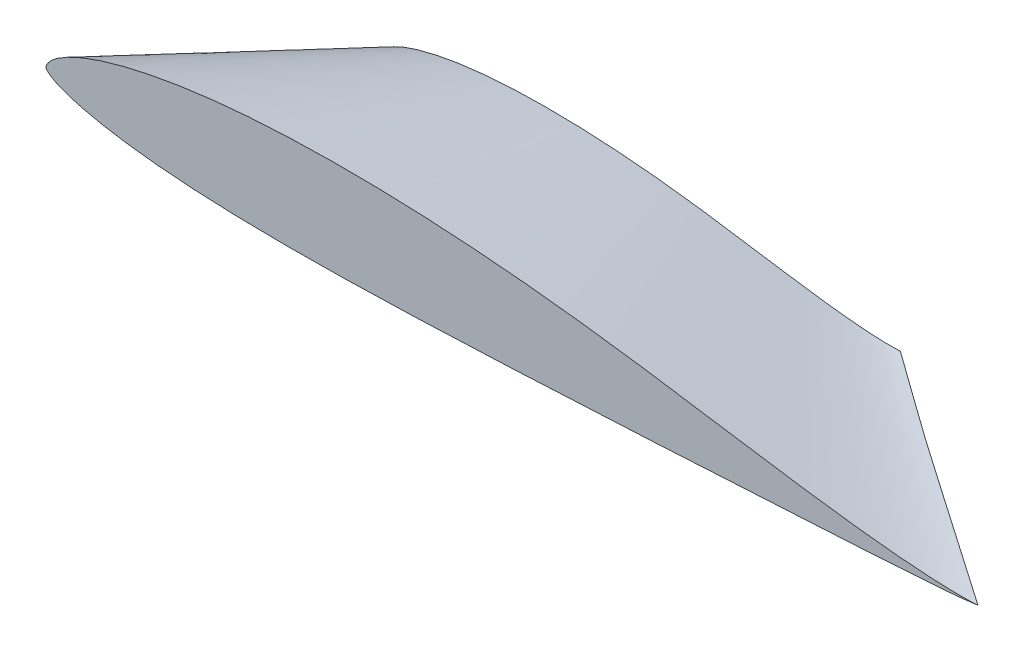
SolidWorks part; units mm, degrees
ref_plane "Front Plane" through (0, 0, 0) normal (0, 0, 1) x (1, 0, 0)
ref_plane "Top Plane" through (0, 0, 0) normal (0, 1, 0) x (1, 0, 0)
ref_plane "Right Plane" through (0, 0, 0) normal (1, 0, 0) x (0, 0, -1)
curve "Curve1"
  spline degree 3 poles (178.8235, -0.1536, 0) (180.3162, 0.0326, 0) (178.6769, -0.0979, 0) (177.3268, -0.1109, 0) (173.9976, -0.1057, 0) (169.9397, 0.1046, 0) (164.6882, 0.4858, 0) (158.5901, 1.1026, 0) (151.6988, 1.9482, 0) (144.1808, 2.9934, 0) (136.1635, 4.1927, 0) (127.7797, 5.4908, 0) (119.1442, 6.8173, 0) (110.3463, 8.0754, 0) (101.4587, 9.2, 0) (92.5465, 10.1562, 0) (83.6758, 10.9156, 0) (74.9166, 11.4682, 0) (66.342, 11.806, 0) (58.028, 11.9274, 0) (50.0487, 11.8319, 0) (42.4741, 11.515, 0) (35.367, 10.9819, 0) (28.7822, 10.24, 0) (22.7701, 9.3088, 0) (17.3773, 8.2269, 0) (12.6499, 7.0268, 0) (8.6305, 5.74, 0) (5.3502, 4.4039, 0) (2.8359, 3.0632, 0) (1.2518, 1.9009, 0) (0.4818, 1.0554, 0) (0.1891, 0.6046, 0) (0.0579, 0.3158, 0) (-0.0016, 0.0856, 0) (-0.0042, -0.0985, 0) (0.0738, -0.2696, 0) (0.2282, -0.4702, 0) (0.4808, -0.7088, 0) (0.9335, -1.0446, 0) (2.0075, -1.6855, 0) (4.0408, -2.5002, 0) (7.1529, -3.4084, 0) (11.097, -4.2605, 0) (15.8307, -5.0186, 0) (21.3187, -5.6503, 0) (27.5191, -6.1332, 0) (34.3853, -6.4628, 0) (41.8623, -6.6344, 0) (49.8874, -6.6565, 0) (58.3886, -6.5391, 0) (67.2847, -6.306, 0) (76.4836, -5.9763, 0) (85.8843, -5.5795, 0) (95.3777, -5.1338, 0) (104.8501, -4.6614, 0) (114.1865, -4.1746, 0) (123.2728, -3.6881, 0) (131.998, -3.2085, 0) (140.2557, -2.7461, 0) (147.9458, -2.3044, 0) (154.9716, -1.8945, 0) (161.2526, -1.5152, 0) (166.6878, -1.1747, 0) (171.2749, -0.8603, 0) (174.7811, -0.5984, 0) (177.6251, -0.3216, 0) (178.8235, -0.1536, 0) (180.3162, 0.0326, 0) (178.6769, -0.0979, 0) knots -0.013312 -0.00609 -0.00158 0 0.001669 0.006747 0.015187 0.026742 0.041155 0.058129 0.077283 0.098227 0.12058 0.143966 0.168018 0.192451 0.217075 0.24171 0.266182 0.29031 0.313903 0.336767 0.358704 0.37954 0.399122 0.417322 0.434037 0.449154 0.462553 0.474139 0.483848 0.491647 0.497539 0.499898 0.501005 0.501951 0.502492 0.502956 0.503431 0.504004 0.505035 0.506276 0.508636 0.515301 0.524213 0.535296 0.548467 0.563638 0.580726 0.599619 0.62018 0.642246 0.665633 0.690118 0.715452 0.741354 0.76752 0.793634 0.819375 0.844429 0.868488 0.891259 0.912467 0.93185 0.949165 0.964196 0.976755 0.986688 0.99391 0.99842 1 1.001669 1.006747 1.015187 periodic
ref_plane "Plane1" through (0, 0, -35) normal (0, 0, 1) x (1, 0, 0)
sketch "Sketch2" plane through (0, 0, 0) normal (0, 0, 1) x (1, 0, 0)
  line L0 (180, 0) -> (0, 0) construction
  spline S0 degree 3 poles (178.8235, -0.1536) (180.3162, 0.0326) (178.6769, -0.0979) (177.3268, -0.1109) (173.9976, -0.1057) (169.9397, 0.1046) (164.6882, 0.4858) (158.5901, 1.1026) (151.6988, 1.9482) (144.1808, 2.9934) (136.1635, 4.1927) (127.7797, 5.4908) (119.1442, 6.8173) (110.3463, 8.0754) (101.4587, 9.2) (92.5465, 10.1562) (83.6758, 10.9156) (74.9166, 11.4682) (66.342, 11.806) (58.028, 11.9274) (50.0487, 11.8319) (42.4741, 11.515) (35.367, 10.9819) (28.7822, 10.24) (22.7701, 9.3088) (17.3773, 8.2269) (12.6499, 7.0268) (8.6305, 5.74) (5.3502, 4.4039) (2.8359, 3.0632) (1.2518, 1.9009) (0.4818, 1.0554) (0.1891, 0.6046) (0.0579, 0.3158) (-0.0016, 0.0856) (-0.0042, -0.0985) (0.0738, -0.2696) (0.2282, -0.4702) (0.4808, -0.7088) (0.9335, -1.0446) (2.0075, -1.6855) (4.0408, -2.5002) (7.1529, -3.4084) (11.097, -4.2605) (15.8307, -5.0186) (21.3187, -5.6503) (27.5191, -6.1332) (34.3853, -6.4628) (41.8623, -6.6344) (49.8874, -6.6565) (58.3886, -6.5391) (67.2847, -6.306) (76.4836, -5.9763) (85.8843, -5.5795) (95.3777, -5.1338) (104.8501, -4.6614) (114.1865, -4.1746) (123.2728, -3.6881) (131.998, -3.2085) (140.2557, -2.7461) (147.9458, -2.3044) (154.9716, -1.8945) (161.2526, -1.5152) (166.6878, -1.1747) (171.2749, -0.8603) (174.7811, -0.5984) (177.6251, -0.3216) (178.8235, -0.1536) (180.3162, 0.0326) (178.6769, -0.0979) knots -0.013312 -0.00609 -0.00158 0 0.001669 0.006747 0.015187 0.026742 0.041155 0.058129 0.077283 0.098227 0.12058 0.143966 0.168018 0.192451 0.217075 0.24171 0.266182 0.29031 0.313903 0.336767 0.358704 0.37954 0.399122 0.417322 0.434037 0.449154 0.462553 0.474139 0.483848 0.491647 0.497539 0.499898 0.501005 0.501951 0.502492 0.502956 0.503431 0.504004 0.505035 0.506276 0.508636 0.515301 0.524213 0.535296 0.548467 0.563638 0.580726 0.599619 0.62018 0.642246 0.665633 0.690118 0.715452 0.741354 0.76752 0.793634 0.819375 0.844429 0.868488 0.891259 0.912467 0.93185 0.949165 0.964196 0.976755 0.986688 0.99391 0.99842 1 1.001669 1.006747 1.015187 only from (180, 0) to (180, 0) construction
  spline S1 degree 3 poles (178.8235, -0.1536) (180.3162, 0.0326) (178.6769, -0.0979) (177.3268, -0.1109) (173.9976, -0.1057) (169.9397, 0.1046) (164.6882, 0.4858) (158.5901, 1.1026) (151.6988, 1.9482) (144.1808, 2.9934) (136.1635, 4.1927) (127.7797, 5.4908) (119.1442, 6.8173) (110.3463, 8.0754) (101.4587, 9.2) (92.5465, 10.1562) (83.6758, 10.9156) (74.9166, 11.4682) (66.342, 11.806) (58.028, 11.9274) (50.0487, 11.8319) (42.4741, 11.515) (35.367, 10.9819) (28.7822, 10.24) (22.7701, 9.3088) (17.3773, 8.2269) (12.6499, 7.0268) (8.6305, 5.74) (5.3502, 4.4039) (2.8359, 3.0632) (1.2518, 1.9009) (0.4818, 1.0554) (0.1891, 0.6046) (0.0579, 0.3158) (-0.0016, 0.0856) (-0.0042, -0.0985) (0.0738, -0.2696) (0.2282, -0.4702) (0.4808, -0.7088) (0.9335, -1.0446) (2.0075, -1.6855) (4.0408, -2.5002) (7.1529, -3.4084) (11.097, -4.2605) (15.8307, -5.0186) (21.3187, -5.6503) (27.5191, -6.1332) (34.3853, -6.4628) (41.8623, -6.6344) (49.8874, -6.6565) (58.3886, -6.5391) (67.2847, -6.306) (76.4836, -5.9763) (85.8843, -5.5795) (95.3777, -5.1338) (104.8501, -4.6614) (114.1865, -4.1746) (123.2728, -3.6881) (131.998, -3.2085) (140.2557, -2.7461) (147.9458, -2.3044) (154.9716, -1.8945) (161.2526, -1.5152) (166.6878, -1.1747) (171.2749, -0.8603) (174.7811, -0.5984) (177.6251, -0.3216) (178.8235, -0.1536) (180.3162, 0.0326) (178.6769, -0.0979) knots -0.013312 -0.00609 -0.00158 0 0.001669 0.006747 0.015187 0.026742 0.041155 0.058129 0.077283 0.098227 0.12058 0.143966 0.168018 0.192451 0.217075 0.24171 0.266182 0.29031 0.313903 0.336767 0.358704 0.37954 0.399122 0.417322 0.434037 0.449154 0.462553 0.474139 0.483848 0.491647 0.497539 0.499898 0.501005 0.501951 0.502492 0.502956 0.503431 0.504004 0.505035 0.506276 0.508636 0.515301 0.524213 0.535296 0.548467 0.563638 0.580726 0.599619 0.62018 0.642246 0.665633 0.690118 0.715452 0.741354 0.76752 0.793634 0.819375 0.844429 0.868488 0.891259 0.912467 0.93185 0.949165 0.964196 0.976755 0.986688 0.99391 0.99842 1 1.001669 1.006747 1.015187 only from (180, 0) to (180, 0)
  point P4 (0, 0)
curve "Curve2"
  spline degree 3 poles (129.3464, -0.0853, 0) (130.1757, 0.0181, 0) (129.2649, -0.0544, 0) (128.5149, -0.0616, 0) (126.6653, -0.0587, 0) (124.4109, 0.0581, 0) (121.4935, 0.2699, 0) (118.1056, 0.6125, 0) (114.2771, 1.0823, 0) (110.1004, 1.663, 0) (105.6464, 2.3293, 0) (100.9887, 3.0504, 0) (96.1912, 3.7874, 0) (91.3035, 4.4863, 0) (86.366, 5.1111, 0) (81.4147, 5.6423, 0) (76.4865, 6.0642, 0) (71.6203, 6.3712, 0) (66.8567, 6.5589, 0) (62.2378, 6.6263, 0) (57.8048, 6.5733, 0) (53.5967, 6.3972, 0) (49.6483, 6.1011, 0) (45.9901, 5.6889, 0) (42.65, 5.1716, 0) (39.654, 4.5705, 0) (37.0277, 3.9038, 0) (34.7947, 3.1889, 0) (32.9723, 2.4466, 0) (31.5755, 1.7018, 0) (30.6954, 1.0561, 0) (30.2677, 0.5864, 0) (30.1051, 0.3359, 0) (30.0322, 0.1755, 0) (29.9991, 0.0476, 0) (29.9977, -0.0547, 0) (30.041, -0.1498, 0) (30.1268, -0.2612, 0) (30.2671, -0.3938, 0) (30.5186, -0.5803, 0) (31.1153, -0.9364, 0) (32.2449, -1.389, 0) (33.9738, -1.8935, 0) (36.165, -2.3669, 0) (38.7949, -2.7881, 0) (41.8437, -3.1391, 0) (45.2884, -3.4073, 0) (49.1029, -3.5905, 0) (53.2568, -3.6858, 0) (57.7152, -3.6981, 0) (62.4381, -3.6328, 0) (67.3804, -3.5033, 0) (72.4909, -3.3202, 0) (77.7135, -3.0997, 0) (82.9876, -2.8521, 0) (88.2501, -2.5897, 0) (93.437, -2.3192, 0) (98.4849, -2.0489, 0) (103.3322, -1.7825, 0) (107.9198, -1.5256, 0) (112.1921, -1.2802, 0) (116.0954, -1.0525, 0) (119.5848, -0.8418, 0) (122.6043, -0.6526, 0) (125.1527, -0.4779, 0) (127.1006, -0.3325, 0) (128.6806, -0.1786, 0) (129.3464, -0.0853, 0) (130.1757, 0.0181, 0) (129.2649, -0.0544, 0) knots -0.013312 -0.00609 -0.00158 0 0.001669 0.006747 0.015187 0.026742 0.041155 0.058129 0.077283 0.098227 0.12058 0.143966 0.168018 0.192451 0.217075 0.24171 0.266182 0.29031 0.313903 0.336767 0.358704 0.37954 0.399122 0.417322 0.434037 0.449154 0.462553 0.474139 0.483848 0.491647 0.497539 0.499898 0.501005 0.501951 0.502492 0.502956 0.503431 0.504004 0.505035 0.506276 0.508636 0.515301 0.524213 0.535296 0.548467 0.563638 0.580726 0.599619 0.62018 0.642246 0.665633 0.690118 0.715452 0.741354 0.76752 0.793634 0.819375 0.844429 0.868488 0.891259 0.912467 0.93185 0.949165 0.964196 0.976755 0.986688 0.99391 0.99842 1 1.001669 1.006747 1.015187 periodic
sketch "Sketch3" plane through (0, 0, -35) normal (0, 0, 1) x (1, 0, 0)
  line L0 (130, 0) -> (29.9996, 0) construction
  spline S0 degree 3 poles (129.3464, -0.0853) (130.1757, 0.0181) (129.2649, -0.0544) (128.5149, -0.0616) (126.6653, -0.0587) (124.4109, 0.0581) (121.4935, 0.2699) (118.1056, 0.6125) (114.2771, 1.0823) (110.1004, 1.663) (105.6464, 2.3293) (100.9887, 3.0504) (96.1912, 3.7874) (91.3035, 4.4863) (86.366, 5.1111) (81.4147, 5.6423) (76.4865, 6.0642) (71.6203, 6.3712) (66.8567, 6.5589) (62.2378, 6.6263) (57.8048, 6.5733) (53.5967, 6.3972) (49.6483, 6.1011) (45.9901, 5.6889) (42.65, 5.1716) (39.654, 4.5705) (37.0277, 3.9038) (34.7947, 3.1889) (32.9723, 2.4466) (31.5755, 1.7018) (30.6954, 1.0561) (30.2677, 0.5864) (30.1051, 0.3359) (30.0322, 0.1755) (29.9991, 0.0476) (29.9977, -0.0547) (30.041, -0.1498) (30.1268, -0.2612) (30.2671, -0.3938) (30.5186, -0.5803) (31.1153, -0.9364) (32.2449, -1.389) (33.9738, -1.8935) (36.165, -2.3669) (38.7949, -2.7881) (41.8437, -3.1391) (45.2884, -3.4073) (49.1029, -3.5905) (53.2568, -3.6858) (57.7152, -3.6981) (62.4381, -3.6328) (67.3804, -3.5033) (72.4909, -3.3202) (77.7135, -3.0997) (82.9876, -2.8521) (88.2501, -2.5897) (93.437, -2.3192) (98.4849, -2.0489) (103.3322, -1.7825) (107.9198, -1.5256) (112.1921, -1.2802) (116.0954, -1.0525) (119.5848, -0.8418) (122.6043, -0.6526) (125.1527, -0.4779) (127.1006, -0.3325) (128.6806, -0.1786) (129.3464, -0.0853) (130.1757, 0.0181) (129.2649, -0.0544) knots -0.013312 -0.00609 -0.00158 0 0.001669 0.006747 0.015187 0.026742 0.041155 0.058129 0.077283 0.098227 0.12058 0.143966 0.168018 0.192451 0.217075 0.24171 0.266182 0.29031 0.313903 0.336767 0.358704 0.37954 0.399122 0.417322 0.434037 0.449154 0.462553 0.474139 0.483848 0.491647 0.497539 0.499898 0.501005 0.501951 0.502492 0.502956 0.503431 0.504004 0.505035 0.506276 0.508636 0.515301 0.524213 0.535296 0.548467 0.563638 0.580726 0.599619 0.62018 0.642246 0.665633 0.690118 0.715452 0.741354 0.76752 0.793634 0.819375 0.844429 0.868488 0.891259 0.912467 0.93185 0.949165 0.964196 0.976755 0.986688 0.99391 0.99842 1 1.001669 1.006747 1.015187 only from (130, 0) to (130, 0) construction
  spline S1 degree 3 poles (129.3464, -0.0853) (130.1757, 0.0181) (129.2649, -0.0544) (128.5149, -0.0616) (126.6653, -0.0587) (124.4109, 0.0581) (121.4935, 0.2699) (118.1056, 0.6125) (114.2771, 1.0823) (110.1004, 1.663) (105.6464, 2.3293) (100.9887, 3.0504) (96.1912, 3.7874) (91.3035, 4.4863) (86.366, 5.1111) (81.4147, 5.6423) (76.4865, 6.0642) (71.6203, 6.3712) (66.8567, 6.5589) (62.2378, 6.6263) (57.8048, 6.5733) (53.5967, 6.3972) (49.6483, 6.1011) (45.9901, 5.6889) (42.65, 5.1716) (39.654, 4.5705) (37.0277, 3.9038) (34.7947, 3.1889) (32.9723, 2.4466) (31.5755, 1.7018) (30.6954, 1.0561) (30.2677, 0.5864) (30.1051, 0.3359) (30.0322, 0.1755) (29.9991, 0.0476) (29.9977, -0.0547) (30.041, -0.1498) (30.1268, -0.2612) (30.2671, -0.3938) (30.5186, -0.5803) (31.1153, -0.9364) (32.2449, -1.389) (33.9738, -1.8935) (36.165, -2.3669) (38.7949, -2.7881) (41.8437, -3.1391) (45.2884, -3.4073) (49.1029, -3.5905) (53.2568, -3.6858) (57.7152, -3.6981) (62.4381, -3.6328) (67.3804, -3.5033) (72.4909, -3.3202) (77.7135, -3.0997) (82.9876, -2.8521) (88.2501, -2.5897) (93.437, -2.3192) (98.4849, -2.0489) (103.3322, -1.7825) (107.9198, -1.5256) (112.1921, -1.2802) (116.0954, -1.0525) (119.5848, -0.8418) (122.6043, -0.6526) (125.1527, -0.4779) (127.1006, -0.3325) (128.6806, -0.1786) (129.3464, -0.0853) (130.1757, 0.0181) (129.2649, -0.0544) knots -0.013312 -0.00609 -0.00158 0 0.001669 0.006747 0.015187 0.026742 0.041155 0.058129 0.077283 0.098227 0.12058 0.143966 0.168018 0.192451 0.217075 0.24171 0.266182 0.29031 0.313903 0.336767 0.358704 0.37954 0.399122 0.417322 0.434037 0.449154 0.462553 0.474139 0.483848 0.491647 0.497539 0.499898 0.501005 0.501951 0.502492 0.502956 0.503431 0.504004 0.505035 0.506276 0.508636 0.515301 0.524213 0.535296 0.548467 0.563638 0.580726 0.599619 0.62018 0.642246 0.665633 0.690118 0.715452 0.741354 0.76752 0.793634 0.819375 0.844429 0.868488 0.891259 0.912467 0.93185 0.949165 0.964196 0.976755 0.986688 0.99391 0.99842 1 1.001669 1.006747 1.015187 only from (130, 0) to (130, 0)
loft "Loft1" add profiles "Sketch2", "Sketch3" connector at (55.3868, 11.8834, 0) connector at (61.3985, 6.6053, -35)
mirror "Mirror1" [suppressed] about plane through (0, 0, 0) normal (0, 0, 1)
ref_axis "Axis4" through (0, 0, -61.6271) along (0, 0, 1)
ref_axis "Axis1" through (180, 0, 0) along (-1, 0, 0)
ref_axis "Axis2" through (130, 0, -35) along (-1, 0, 0)
ref_point "Point1"
ref_axis "Axis3" through (-0.0007, 0, 0) along (0.6508, 0, -0.7593)
sketch "Sketch4" plane through (0, 0, 0) normal (0, 1, 0) x (1, 0, 0)
  line L0 (0, 0) -> (141.8779, 107.8393) construction
  line L1 (0, 0) -> (100, 360) construction
  line L3 (25.3509, 91.2632) -> (60.0348, 45.6316) construction
  line L4 (94.7187, 0) -> (60.0348, 45.6316) construction
  line L5 (180, 0) -> (0, 0) construction
  dimension "D1" = 360
  dimension "D2" = 100
ref_plane "Plane2" through (0, 0, 0) normal (0.6051, 0, 0.7961) x (0.7961, 0, -0.6051)
sketch "Sketch5" plane through (0, 0, 0) normal (0.6051, 0, 0.7961) x (0.7961, 0, -0.6051)
  line L0 (42.0724, -26.6467) -> (53.5834, 38.635) construction
  line L1 (42.0724, -26.6467) -> (42.0724, 24.9899) construction
  point P3 (42.0724, -26.6467)
  dimension "D1" = 10
ref_axis "Axis5" through (33.623, -25.7352, -25.5564) along (0.1382, 0.9848, -0.1051)
ref_point "Point2"
